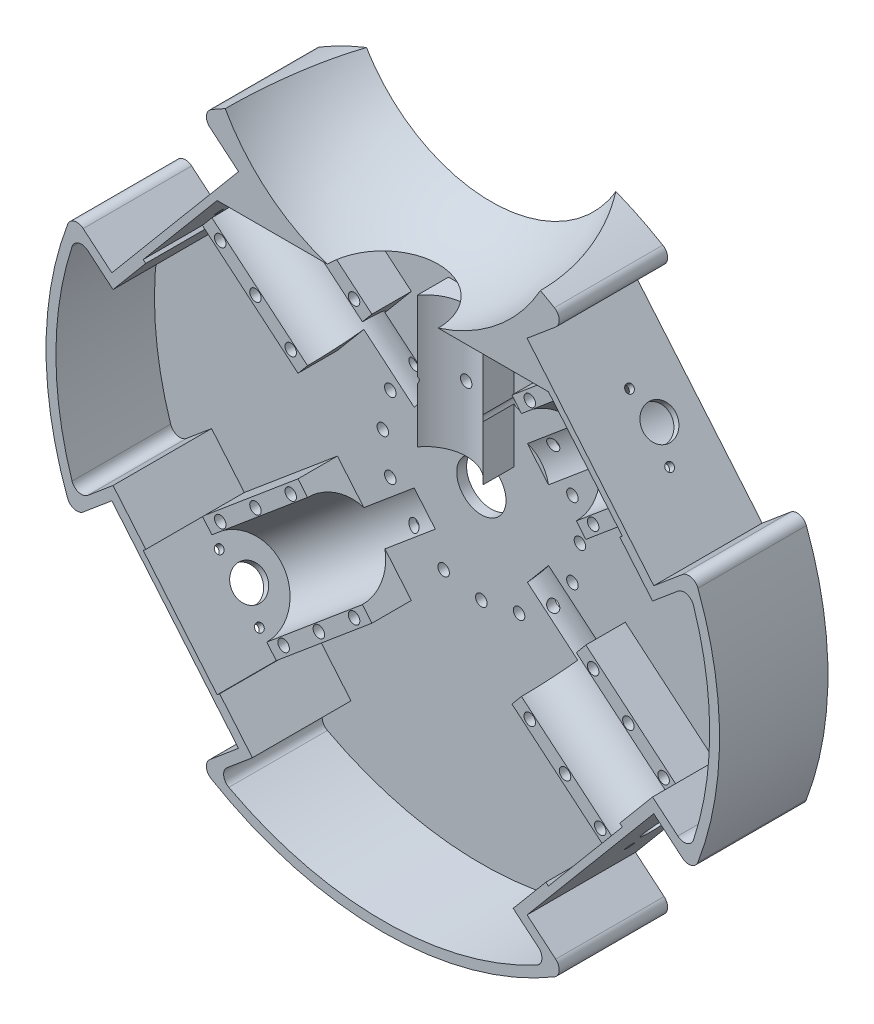
SolidWorks part; units mm, degrees
ref_plane "Front Plane" through (0, 0, 0) normal (0, 0, 1) x (1, 0, 0)
ref_plane "Top Plane" through (0, 0, 0) normal (0, 1, 0) x (1, 0, 0)
ref_plane "Right Plane" through (0, 0, 0) normal (1, 0, 0) x (0, 0, -1)
sketch "Sketch1" plane through (0, 0, 0) normal (0, 0, 1) x (1, 0, 0)
  circle A0 centre (0, 0) radius 102.5
  dimension "D1" = 205
extrude "Boss-Extrude1" add sketch "Sketch1" along normal blind 3
sketch "Sketch2" plane through (0, 0, 3) normal (0, 0, 1) x (1, 0, 0)
  line L0 (78.5196, 65.8857) -> (0, 0) construction
  line L1 (0, 0) -> (102.5, 0) construction
  line L2 (74.5568, 101.7228) -> (113.1241, 55.7601)
  line L3 (74.5568, 101.7228) -> (43.915, 76.0113)
  line L4 (113.1241, 55.7601) -> (82.4823, 30.0486)
  line L5 (43.915, 76.0113) -> (82.4823, 30.0486)
  line L6 (74.5568, 101.7228) -> (82.4823, 30.0486) construction
  line L7 (113.1241, 55.7601) -> (43.915, 76.0113) construction
  circle A0 centre (0, 0) radius 102.5 construction
  dimension "D1" = 40
  dimension "D2" = 60
  dimension "D3" = 40
extrude "Cut-Extrude1" cut sketch "Sketch2" against normal blind 3
sketch "Sketch3" plane through (0, 0, 3) normal (0, 0, 1) x (1, 0, 0)
  line L0 (51.9499, 66.4358) -> (74.4474, 39.6242)
  line L1 (51.9499, 66.4358) -> (21.3081, 40.7243)
  line L2 (74.4474, 39.6242) -> (43.8057, 13.9127)
  line L3 (21.3081, 40.7243) -> (43.8057, 13.9127)
  line L4 (43.915, 76.0113) -> (82.4823, 30.0486) construction
  point P6 (63.1987, 53.03)
  dimension "D1" = 35
  dimension "D2" = 40
extrude "Boss-Extrude2" add sketch "Sketch3" along normal blind 12
sketch "Sketch4" plane through (63.1987, 53.03, 0) normal (0.766, 0.6428, 0) x (0, 0, -1)
  line L0 (-15, -17.5) -> (-15, 17.5) construction
  circle A0 centre (-15, 0) radius 13
  dimension "D1" = 26
extrude "Cut-Extrude2" cut sketch "Sketch4" against normal blind 60
sketch "Sketch5" plane through (0, 0, 15) normal (0, 0, 1) x (1, 0, 0)
  line L0 (26.7453, 42.0231) -> (48.1945, 60.0211) construction
  line L1 (26.7453, 42.0231) -> (46.0289, 19.0417) construction
  line L2 (48.1945, 60.0211) -> (67.4782, 37.0398) construction
  line L3 (46.0289, 19.0417) -> (67.4782, 37.0398) construction
  line L4 (51.9499, 66.4358) -> (21.3081, 40.7243) construction
  line L5 (71.5549, 43.0714) -> (54.8424, 62.9886) construction
  line L6 (21.3081, 40.7243) -> (29.343, 31.1487) construction
  line L7 (57.8364, 48.5305) -> (63.1987, 53.03) construction
  circle A0 centre (26.7453, 42.0231) radius 1.75
  circle A1 centre (37.4699, 51.0221) radius 1.75
  circle A2 centre (48.1945, 60.0211) radius 1.75
  circle A3 centre (67.4782, 37.0398) radius 1.75
  circle A4 centre (56.7535, 28.0408) radius 1.75
  circle A5 centre (46.0289, 19.0417) radius 1.75
  dimension "D4" = 3.5
  dimension "D1" = 7
  dimension "D2" = 5
  dimension "D3" = 30
extrude "Cut-Extrude3" cut sketch "Sketch5" against normal through all
sketch "Sketch6" plane through (0, 0, 3) normal (0, 0, 1) x (1, 0, 0)
  line L0 (51.9499, 66.4358) -> (74.4474, 39.6242)
  line L1 (51.9499, 66.4358) -> (50.4178, 65.1502)
  line L2 (74.4474, 39.6242) -> (72.9154, 38.3386)
  line L3 (50.4178, 65.1502) -> (72.9154, 38.3386)
  dimension "D1" = 2
extrude "Boss-Extrude3" add sketch "Sketch6" along normal blind 30 and the other way blind 3
sketch "Sketch7" plane through (63.1987, 53.03, 0) normal (0.766, 0.6428, 0) x (0, 0, -1)
  line L0 (-15, 17.5) -> (-15, -17.5) construction
  line L1 (-33, 17.5) -> (-3, 17.5) construction
  line L2 (-33, -17.5) -> (-3, -17.5) construction
  line L3 (-15, 0) -> (-12, 0) construction
  line L4 (-3, 30) -> (-3, 17.5) construction
  circle A0 centre (-12, 0) radius 5
  circle A1 centre (-15, 9.5) radius 1.25
  circle A2 centre (-15, -9.5) radius 1.25
  dimension "D2" = 10
  dimension "D6" = 2.5
  dimension "D1" = 12
  dimension "D3" = 3
  dimension "D4" = 9.5
  dimension "D5" = 9.5
extrude "Cut-Extrude4" cut sketch "Sketch7" against normal blind 2
mirror "Mirror1" about plane through (0, 0, 0) normal (1, 0, 0) of "Cut-Extrude4", "Boss-Extrude3", "Cut-Extrude3", "Cut-Extrude2", "Boss-Extrude2", "Cut-Extrude1" second plane through (0, 0, 0) second plane normal (0, 1, 0)
sketch "Sketch8" plane through (0, 0, 3) normal (0, 0, 1) x (1, 0, 0)
  line L0 (74.4474, 39.6242) -> (82.4823, 30.0486) construction
  line L1 (82.4823, 30.0486) -> (94.3648, 40.0192) construction
  line L2 (82.4823, -30.0486) -> (94.3648, -40.0192) construction
  line L3 (74.4474, -39.6242) -> (82.4823, -30.0486) construction
  line L4 (43.915, -76.0113) -> (51.9499, -66.4358) construction
  line L5 (55.7975, -85.9819) -> (43.915, -76.0113) construction
  line L6 (-55.7975, -85.9819) -> (-43.915, -76.0113) construction
  line L7 (-43.915, -76.0113) -> (-51.9499, -66.4358) construction
  line L8 (-74.4474, 39.6242) -> (-82.4823, 30.0486) construction
  line L9 (-82.4823, 30.0486) -> (-94.3648, 40.0192) construction
  line L10 (-74.4474, -39.6242) -> (-82.4823, -30.0486) construction
  line L11 (-82.4823, -30.0486) -> (-94.3648, -40.0192) construction
  line L12 (74.4474, 39.6242) -> (82.4823, 30.0486)
  line L13 (82.4823, 30.0486) -> (94.3648, 40.0192)
  line L14 (82.4823, -30.0486) -> (94.3648, -40.0192)
  line L15 (74.4474, -39.6242) -> (82.4823, -30.0486)
  line L16 (43.915, -76.0113) -> (51.9499, -66.4358)
  line L17 (55.7975, -85.9819) -> (43.915, -76.0113)
  line L18 (-55.7975, -85.9819) -> (-43.915, -76.0113)
  line L19 (-43.915, -76.0113) -> (-51.9499, -66.4358)
  line L20 (-74.4474, 39.6242) -> (-82.4823, 30.0486)
  line L21 (-82.4823, 30.0486) -> (-94.3648, 40.0192)
  line L22 (-74.4474, -39.6242) -> (-82.4823, -30.0486)
  line L23 (-82.4823, -30.0486) -> (-94.3648, -40.0192)
  line L24 (72.1493, 37.6958) -> (82.1125, 25.8221)
  line L25 (82.1125, 25.8221) -> (93.1192, 35.0579)
  line L26 (82.1125, -25.8221) -> (93.1192, -35.0579)
  line L27 (72.1493, -37.6958) -> (82.1125, -25.8221)
  line L28 (-39.6885, -76.3811) -> (-49.6518, -64.5074)
  line L29 (-50.6953, -85.6168) -> (-39.6885, -76.3811)
  line L30 (50.6953, -85.6168) -> (39.6885, -76.3811)
  line L31 (39.6885, -76.3811) -> (49.6518, -64.5074)
  line L32 (-72.1493, 37.6958) -> (-82.1125, 25.8221)
  line L33 (-82.1125, 25.8221) -> (-93.1192, 35.0579)
  line L34 (-82.1125, -25.8221) -> (-93.1192, -35.0579)
  line L35 (-72.1493, -37.6958) -> (-82.1125, -25.8221)
  line L36 (-74.4474, 39.6242) -> (-72.1493, 37.6958)
  line L37 (-74.4474, -39.6242) -> (-72.1493, -37.6958)
  line L38 (-51.9499, -66.4358) -> (-49.6518, -64.5074)
  line L39 (49.6518, -64.5074) -> (51.9499, -66.4358)
  line L40 (72.1493, -37.6958) -> (74.4474, -39.6242)
  line L41 (72.1493, 37.6958) -> (74.4474, 39.6242)
  arc A0 (94.3648, -40.0192) -> (94.3648, 40.0192) centre (0, 0) ccw construction
  arc A1 (-55.7975, -85.9819) -> (55.7975, -85.9819) centre (0, 0) ccw construction
  arc A2 (-94.3648, 40.0192) -> (-94.3648, -40.0192) centre (0, 0) ccw construction
  arc A3 (94.3648, -40.0192) -> (94.3648, 40.0192) centre (0, 0) ccw
  arc A4 (-55.7975, -85.9819) -> (55.7975, -85.9819) centre (0, 0) ccw
  arc A5 (-94.3648, 40.0192) -> (-94.3648, -40.0192) centre (0, 0) ccw
  arc A6 (93.1192, -35.0579) -> (93.1192, 35.0579) centre (0, 0) ccw
  arc A7 (-50.6953, -85.6168) -> (50.6953, -85.6168) centre (0, 0) ccw
  arc A8 (-93.1192, 35.0579) -> (-93.1192, -35.0579) centre (0, 0) ccw
  dimension "D1" = 3
  dimension "D2" = 3
extrude "Boss-Extrude4" add sketch "Sketch8" along normal blind 30
sketch "Sketch9" plane through (0, 0, 3) normal (0, 0, 1) x (1, 0, 0)
  line L0 (43.915, 76.0113) -> (51.9499, 66.4358) construction
  line L1 (-43.915, 76.0113) -> (-51.9499, 66.4358) construction
  line L2 (55.7975, 85.9819) -> (43.915, 76.0113) construction
  line L3 (-55.7975, 85.9819) -> (-43.915, 76.0113) construction
  line L4 (43.915, 76.0113) -> (51.9499, 66.4358)
  line L5 (-43.915, 76.0113) -> (-51.9499, 66.4358)
  line L6 (55.7975, 85.9819) -> (43.915, 76.0113)
  line L7 (-55.7975, 85.9819) -> (-43.915, 76.0113)
  line L9 (-51.9499, 66.4358) -> (-50.4178, 65.1502)
  line L10 (-50.4178, 65.1502) -> (50.4178, 65.1502)
  line L11 (50.4178, 65.1502) -> (51.9499, 66.4358)
  arc A0 (55.7975, 85.9819) -> (-55.7975, 85.9819) centre (0, 0) ccw construction
  arc A1 (55.7975, 85.9819) -> (-55.7975, 85.9819) centre (0, 0) ccw
extrude "Boss-Extrude6" add sketch "Sketch9" along normal blind 30
sketch "Sketch10" plane through (0, 0, 33) normal (0, 0, 1) x (1, 0, 0)
  line L0 (-55, 117.5) -> (55, 117.5)
  line L1 (0, 117.5) -> (0, 102.5) construction
  arc A1 (-55, 117.5) -> (55, 117.5) centre (0, 117.5) ccw
  arc A2 (55.7975, 85.9819) -> (-55.7975, 85.9819) centre (0, 0) ccw construction
  dimension "D1" = 110
  dimension "D2" = 15
revolve "Cut-Revolve1" cut sketch "Sketch10" angle 360 about L0
fillet "Fillet1" radius 3 14 edges at (-50.6953, -85.6168, 18) (-93.1192, -35.0579, 18) (-93.1192, 35.0579, 18) (-94.3648, 40.0192, 16.5) (-94.3648, -40.0192, 16.5) (-55.7975, -85.9819, 16.5) (50.6953, -85.6168, 18) (55.7975, -85.9819, 16.5) (93.1192, -35.0579, 18) (94.3648, -40.0192, 16.5) (93.1192, 35.0579, 18) (94.3648, 40.0192, 16.5) (-55.7975, 85.9819, 16.5) (55.7975, 85.9819, 16.5)
sketch "Sketch11" plane through (0, 0, 3) normal (0, 0, 1) x (1, 0, 0)
  line L0 (0, 30.1502) -> (0, 0) construction
  line L1 (-10, 50.1502) -> (10, 50.1502)
  line L2 (-10, 50.1502) -> (-10, 10.1502)
  line L3 (-10, 10.1502) -> (10, 10.1502)
  line L4 (10, 50.1502) -> (10, 10.1502)
  line L5 (-10, 50.1502) -> (10, 10.1502) construction
  line L6 (-10, 10.1502) -> (10, 50.1502) construction
  line L7 (16.867, 65.1502) -> (50.4178, 65.1502) construction
  point P0 (0, 30.1502)
  dimension "D1" = 15
  dimension "D2" = 40
  dimension "D3" = 20
extrude "Boss-Extrude7" add sketch "Sketch11" along normal blind 10
sketch "Sketch12" plane through (0, 50.1502, 0) normal (0, 1, 0) x (1, 0, 0)
  line L0 (0, 0) -> (0, -20) construction
  circle A0 centre (0, -20) radius 12.5
  dimension "D1" = 25
  dimension "D2" = 20
extrude "Cut-Extrude5" cut sketch "Sketch12" against normal up to surface (40 mm away) up to face at (0, 10.1502, 8)
sketch "Sketch13" plane through (0, 0, 3) normal (0, 0, 1) x (1, 0, 0)
  line L0 (-30, 0) -> (0, 0) construction
  circle A0 centre (-30, 0) radius 1.75
  circle A1 centre (-27.7164, 11.4805) radius 1.75
  circle A2 centre (-21.2132, 21.2132) radius 1.75
  circle A3 centre (-11.4805, 27.7164) radius 1.75
  circle A4 centre (0, 30) radius 1.75
  circle A5 centre (11.4805, 27.7164) radius 1.75
  circle A6 centre (21.2132, 21.2132) radius 1.75
  circle A7 centre (27.7164, 11.4805) radius 1.75
  circle A8 centre (30, 0) radius 1.75
  circle A9 centre (27.7164, -11.4805) radius 1.75
  circle A10 centre (21.2132, -21.2132) radius 1.75
  circle A11 centre (11.4805, -27.7164) radius 1.75
  circle A12 centre (0, -30) radius 1.75
  circle A13 centre (-11.4805, -27.7164) radius 1.75
  circle A14 centre (-21.2132, -21.2132) radius 1.75
  circle A15 centre (-27.7164, -11.4805) radius 1.75
  circle A16 centre (0, 0) radius 7.5
  point P37 (0, 0)
  dimension "D1" = 3.5
  dimension "D4" = 15
  dimension "D2" = 30
  dimension "D3" = 16
extrude "Cut-Extrude6" cut sketch "Sketch13" against normal through all both and the other way through all
